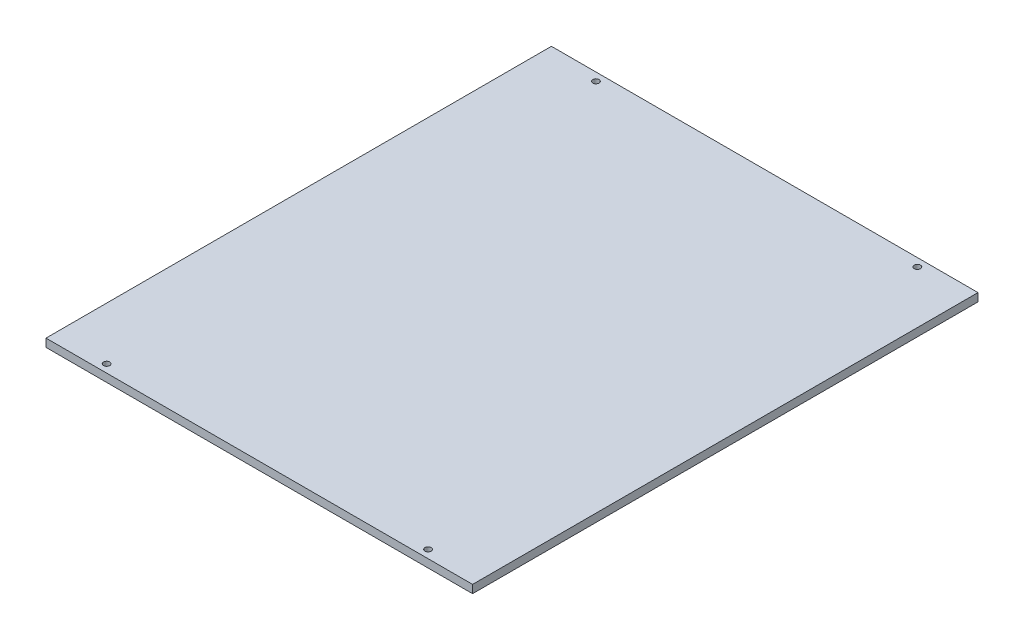
SolidWorks part; units mm, degrees
ref_plane "Front Plane" through (0, 0, 0) normal (0, 0, 1) x (1, 0, 0)
ref_plane "Top Plane" through (0, 0, 0) normal (0, 1, 0) x (1, 0, 0)
ref_plane "Right Plane" through (0, 0, 0) normal (1, 0, 0) x (0, 0, -1)
sketch "Sketch1" plane through (0, 0, 0) normal (0, 1, 0) x (1, 0, 0)
  line L0 (-105.5, 0) -> (-105.5, -250) construction
  line L6 (-211, 0) -> (0, 0)
  line L7 (-211, 0) -> (-211, -250)
  line L16 (-211, -250) -> (0, -250)
  line L21 (0, 0) -> (0, -250)
  line L38 (-211, -125) -> (0, -125) construction
  circle A15 centre (-185, -4) radius 1.55
  circle A16 centre (-185, -246) radius 1.55
  circle A17 centre (-26, -246) radius 1.55
  circle A18 centre (-26, -4) radius 1.55
  dimension "D3" = 3.1
  dimension "D1" = 250
  dimension "D2" = 211
  dimension "D4" = 26
  dimension "D5" = 4
extrude "Boss-Extrude1" add sketch "Sketch1" along normal blind 4
equation "\"cf_tube_outer_diameter\"= 25mm"
equation "\"cf_tube_inner_diameter\" = 21mm"
equation "\"mid_plate_mid_to_top\" = 100mm"
equation "\"mid_plate_mid_to_bottom\" = 30mm"
equation "\"mid_plate_horizontal_spacing\"=250mm"
equation "\"cf_plate_thickness\" =4mm"
equation "\"mid_tube_length\" = 121mm"
equation "\"mid_plate_bottom_width\" = 180mm"
equation "\"mid_support_plate_distance\" = 250mm"
equation "\"nut_strip_2_hole_distance\" = 7mm"
equation "\"nut_strip_hole_diameter\" = 2.5mm"
equation "\"nut_strip_hole_to_edge_distance\"= 2.5mm"
equation "\"D1@Sketch1\"=\"mid_plate_horizontal_spacing\""
equation "\"D1@Boss-Extrude1\"=\"cf_plate_thickness\""
